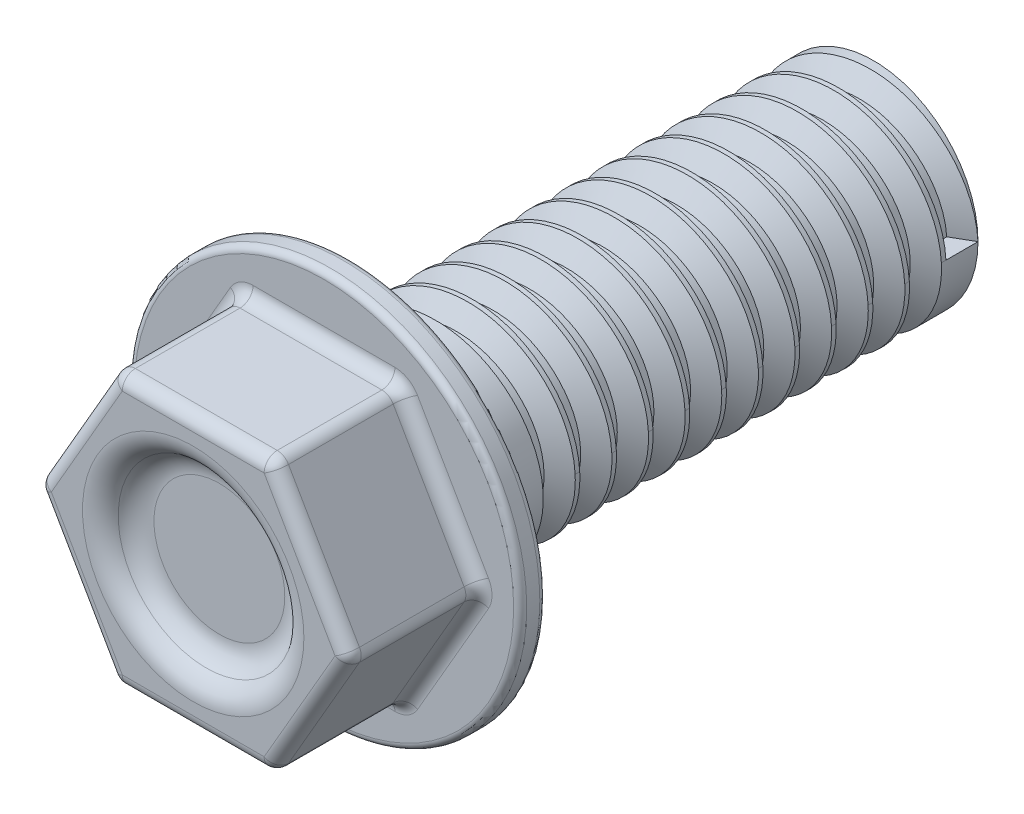
SolidWorks part; units mm, degrees
material "AISI 4140 Steel, quenched & tempered"
ref_plane "Front Plane" through (0, 0, 0) normal (1, 0, 0) x (0, 1, 0)
ref_plane "Top Plane" through (0, 0, 0) normal (0, 0, 1) x (0, 1, 0)
ref_plane "Right Plane" through (0, 0, 0) normal (0, 1, 0) x (-1, 0, 0)
sketch "Sketch1" plane through (0, 0, 0) normal (0, 0, 1) x (0, 1, 0)
  circle A0 centre (0, 0) radius 10
  circle A1 centre (0, 0) radius 15
  circle A2 centre (0, 0) radius 8
  dimension "D1" = 20
  dimension "D2" = 30
  dimension "D3" = 16
extrude "Boss-Extrude1" add sketch "Sketch1" against normal blind 40 contours A2
extrude "Boss-Extrude2" add sketch "Sketch1<3>" along normal blind 2 contours A1
sketch "Sketch1<3>" plane through (0, 0, 0) normal (0, 0, 1) x (0, 1, 0) same geometry as "Sketch1"
sketch "Sketch2" plane through (0, 0, 2) normal (0, 0, 1) x (1, 0, 0)
  line L1 (-12, 0) -> (-6, -10.3923)
  line L2 (-6, -10.3923) -> (6, -10.3923)
  line L3 (6, -10.3923) -> (12, 0)
  line L4 (12, 0) -> (6, 10.3923)
  line L5 (6, 10.3923) -> (-6, 10.3923)
  line L6 (-6, 10.3923) -> (-12, 0)
  circle A0 centre (0, 0) radius 10.3923 construction
  circle A1 centre (0, 0) radius 7
  dimension "D2" = 14
  dimension "D1" = 12
extrude "Boss-Extrude3" add sketch "Sketch2" along normal blind 10 contours L3 L4 L5 L6 L1 L2
extrude "Cut-Extrude1" cut sketch "Sketch2<3>" along normal up to surface (10 mm away) from offset 8 contours A1 up to face at (0, 0, 12)
sketch "Sketch2<3>" plane through (0, 0, 2) normal (0, 0, 1) x (1, 0, 0) same geometry as "Sketch2"
fillet "Fillet1" radius 0.5 2 edges at (15, 0, 0) (15, 0, 2)
fillet "Fillet2" radius 1 18 edges at (-6, -10.3923, 7) (-12, 0, 7) (-6, 10.3923, 7) (6, 10.3923, 7) (6, -10.3923, 7) (12, 0, 7) (-9, -5.1962, 12) (-9, 5.1962, 12) (0, 10.3923, 12) (9, -5.1962, 12) (0, -10.3923, 12) (9, 5.1962, 12) (9, -5.1962, 2) (0, 10.3923, 2) (-9, 5.1962, 2) (-9, -5.1962, 2) (0, -10.3923, 2) (9, 5.1962, 2)
fillet "Fillet3" radius 2 1 edges at (7, 0, 10)
fillet "Fillet4" radius 2 1 edges at (7, 0, 12)
scale "Scale1" scale about centroid uniform scaling yes scale factor 0.25
thread "Thread1" pitch 0.7 method cut profile "Thread Profile1" start angle 0, offset 0, length 8, pitch 0.7, diameter 4
ref_plane "Plane1" through (2, 0, -17.9442) normal (0, -1, 0) x (1, 0, 0)
sketch "Thread Profile1" plane through (2, 0, -17.9442) normal (0, -1, 0) x (1, 0, 0)
  line L0 (0, 0) -> (0, 0.7) construction
  line L11 (0, 0) -> (0, 0.6125)
  line L12 (0, 0.6125) -> (-0.3789, 0.3937)
  line L13 (-0.3789, 0.3937) -> (-0.3789, 0.2187)
  line L15 (-0.3789, 0.2187) -> (0, 0)
  line L17 (-0.3789, 0.3062) -> (0, 0.3062) construction
  point P2 (0, 0)
  dimension "Pitch" = 0.7
  dimension "Profile_Angle" = 60
  dimension "Profile_Land" = 0.175
  dimension "Profile_Height" = 0.3789
